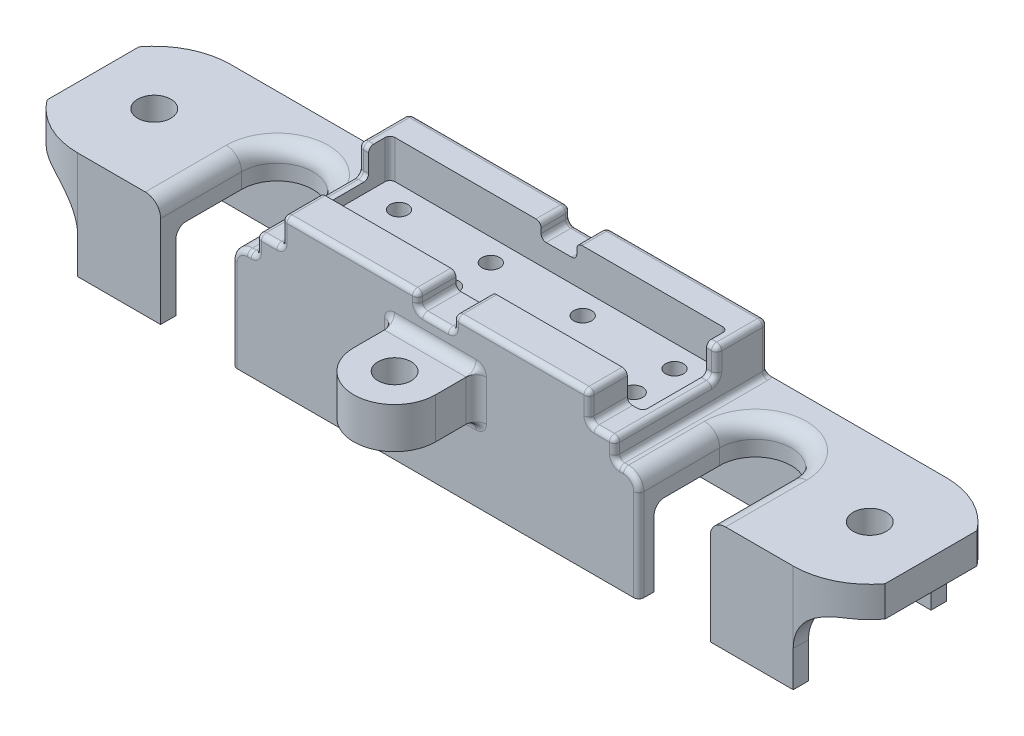
SolidWorks part; units mm, degrees
material "Delrin 2700 NC010, Low Viscosity Acetal Copolymer (SS)"
ref_plane "Front Plane" through (0, 0, 0) normal (0, 0, 1) x (1, 0, 0)
ref_plane "Top Plane" through (0, 0, 0) normal (0, 1, 0) x (1, 0, 0)
ref_plane "Right Plane" through (0, 0, 0) normal (1, 0, 0) x (0, 0, -1)
sketch "Sketch1" plane through (0, 0, 0) normal (0, 1, 0) x (1, 0, 0)
  line L1 (-35.1, -15) -> (0, -15)
  line L2 (-35.1, -15) -> (-35.1, 15)
  line L3 (-35.1, 15) -> (0, 15)
  line L4 (0, -15) -> (0, 15)
  line L5 (-35.1, -15) -> (0, 15) construction
  line L6 (-35.1, 15) -> (0, -15) construction
  point P0 (-17.55, 0)
  point P8 (0, 0)
  dimension "D1" = 35.1
  dimension "D2" = 30
extrude "Boss-Extrude1" add sketch "Sketch1" along normal blind 15.5
shell "Shell1" [suppressed] thickness 1
sketch "Sketch7" plane through (0, 15.5, 0) normal (0, 1, 0) x (1, 0, 0)
  line L0 (0, -15) -> (0, 15) construction
  line L1 (0, -7.5) -> (-33.1, -7.5)
  line L2 (0, -7.5) -> (0, 9.2)
  line L3 (0, 9.2) -> (-33.1, 9.2)
  line L4 (-33.1, -7.5) -> (-33.1, 9.2)
  line L5 (-35.1, -15) -> (0, -15) construction
  line L6 (0, 15) -> (-35.1, 15) construction
  line L7 (-35.1, 15) -> (-35.1, -15) construction
  dimension "D1" = 7.5
  dimension "D2" = 5.8
  dimension "D3" = 2
extrude "Cut-Extrude5" cut sketch "Sketch7" against normal offset from surface (7.5 mm away) 8 up to face at (-17.55, 0, 0)
sketch "Sketch2" plane through (0, 0, 0) normal (0, 1, 0) x (-1, 0, 0)
  line L0 (27, 3.15) -> (9, 3.15) construction
  line L2 (27, 3.15) -> (27, -4.85) construction
  line L3 (27, -4.85) -> (9, -4.85) construction
  line L4 (9, -4.85) -> (9, 3.15) construction
  line L5 (27, -0.85) -> (18.8977, -0.85) construction
  line L6 (17.55, -15) -> (17.55, 15) construction
  line L7 (0, 7.5) -> (0, -9.2) construction
  line L8 (27, -0.85) -> (0, -0.85) construction
  line L9 (0, -15) -> (35.1, -15) construction
  line L10 (35.1, 15) -> (0, 15) construction
  circle A0 centre (27, 3.15) radius 1.75
  circle A1 centre (9, 3.15) radius 1.75
  circle A2 centre (27, -4.85) radius 1.75
  circle A3 centre (9, -4.85) radius 1.75
  circle A5 centre (27, 3.15) radius 2.5 construction
  circle A6 centre (27, -4.85) radius 2.5 construction
  circle A7 centre (9, -4.85) radius 2.5 construction
  circle A8 centre (9, 3.15) radius 2.5 construction
  dimension "D1" = 3.5
  dimension "D4" = 9
  dimension "D5" = 5
  dimension "D2" = 18
  dimension "D3" = 8
extrude "Cut-Extrude1" cut sketch "Sketch2" along normal through all
sketch "Sketch3" [suppressed] plane through (0, 5, 0) normal (0, 1, 0) x (1, 0, 0)
  line L1 (-2.9573, -5.1559) -> (2.9865, -5.139)
  line L2 (2.9865, -5.139) -> (5.9438, 0.0169)
  line L3 (5.9438, 0.0169) -> (2.9573, 5.1559)
  line L4 (2.9573, 5.1559) -> (-2.9865, 5.139)
  line L5 (-2.9865, 5.139) -> (-5.9438, -0.0169)
  line L6 (-5.9438, -0.0169) -> (-2.9573, -5.1559)
  circle A0 centre (0, 0) radius 2.6 construction
  circle A1 centre (0, 0) radius 5.1475 construction
  dimension "D1" = 5.2
extrude "Cut-Extrude2" [suppressed] cut sketch "Sketch3" against normal blind 0.5
sketch "Sketch4" plane through (-35.1, 0, 0) normal (-1, 0, 0) x (0, 0, 1)
  line L0 (-15, 15.5) -> (15, 15.5) construction
  line L1 (-5, 15.5) -> (15, 15.5)
  line L3 (-5, 10) -> (15, 10)
  line L4 (15, 15.5) -> (15, 10)
  line L5 (0, 10) -> (0, 0) construction
  line L11 (-15, 0) -> (15, 0) construction
  line L12 (-5, 10) -> (-5, 15.5)
  dimension "D1" = 5
  dimension "D2" = 5.5
extrude "Cut-Extrude3" cut sketch "Sketch4" against normal offset from surface (5 mm away) 3 up to face at (-33.1, 11.75, -0.85) offset beyond the face yes
sketch "Sketch8" plane through (0, 0, 0) normal (0, -1, 0) x (-1, 0, 0)
  line L0 (35.1, -15) -> (70.1, -15)
  line L1 (35.1, 15) -> (70.1, 15)
  line L2 (35.1, 15) -> (35.1, -15)
  line L3 (82.1, 9) -> (82.1, -9)
  arc A0 (70.1, 15) -> (82.1, 9) centre (70.1, 0) cw
  circle A1 centre (70.1, 0) radius 3.25
  arc A2 (82.1, -9) -> (70.1, -15) centre (70.1, 0) cw
  dimension "D2" = 6.5
  dimension "D1" = 35
  dimension "D3" = 12
extrude "bolt extrude" add sketch "Sketch8" against normal blind 6
mirror "Mirror1" about plane through (0, 0, 0) normal (1, 0, 0) of bodies 112 105
fillet "Fillet3" radius 1 8 edges at (30.1, 10, 11.25) (-30.1, 10, 11.25) (30.1, 15.5, 11.25) (-30.1, 15.5, 11.25) (34.1, 15.5, -5) (34.1, 10, -5) (-34.1, 15.5, -5) (-34.1, 10, -5)
fillet "Fillet5" [suppressed] radius 0.5
sketch "Sketch9" plane through (0, 15.5, 0) normal (0, 1, 0) x (1, 0, 0)
  line L0 (35.1, 15) -> (-35.1, 15) construction
  line L1 (-3.5, 15) -> (3.5, 15)
  line L2 (-3.5, 15) -> (-3.5, -15)
  line L3 (-3.5, -15) -> (3.5, -15)
  line L4 (3.5, 15) -> (3.5, -15)
  line L5 (-29.1, -15) -> (29.1, -15) construction
  dimension "D1" = 3.5
  dimension "D2" = 3.5
extrude "Cut-Extrude6" cut sketch "Sketch9" against normal blind 3
fillet "Fillet6" radius 1 14 edges at (35.1, 10.75, -15) (-35.1, 10.75, -15) (-33.1, 9, 7.5) (-33.1, 11.75, -9.2) (33.1, 11.75, -9.2) (33.1, 9, 7.5) (-3.5, 12.5, -12.1) (3.5, 12.5, -12.1) (3.5, 12.5, 11.25) (-3.5, 12.5, 11.25) (3.5, 15.5, 11.25) (-3.5, 15.5, 11.25) (-3.5, 15.5, -12.1) (3.5, 15.5, -12.1)
fillet "Fillet7" [suppressed] radius 1
fillet "Fillet9" radius 1 25 edges at (-35.1, 10, 5.5) (35.1, 6, 0.5) (34.8071, 6, -14.7071) (35.1, 10, 5.5) (35.1, 10.2929, -4.7071) (35.1, 12.75, -5) (35.1, 15.2071, -5.2929) (35.1, 15.5, -10) (34.8071, 15.5, -14.7071) (19.3, 15.5, -15) (3.7929, 15.2071, -15) (3.5, 14, -15) (3.2071, 12.7929, -15) (0, 12.5, -15) (-3.2071, 12.7929, -15) (-3.5, 14, -15) (-3.7929, 15.2071, -15) (-19.3, 15.5, -15) (-34.8071, 15.5, -14.7071) (-35.1, 15.5, -10) (-35.1, 15.2071, -5.2929) (-35.1, 12.75, -5) (-35.1, 10.2929, -4.7071) (-34.8071, 6, -14.7071) (-35.1, 6, 0.5)
sketch "Sketch11" plane through (0, 0, 0) normal (0, -1, 0) x (1, 0, 0)
  line L0 (70.1, -15) -> (-70.1, -15) construction
  line L1 (-70.1, 15) -> (70.1, 15) construction
  line L2 (70.1, -15) -> (-70.1, -15)
  line L3 (-70.1, 15) -> (70.1, 15)
  line L4 (-70.1, 12) -> (70.1, 12)
  line L5 (70.1, -12) -> (-70.1, -12)
  line L6 (-70.1, 12) -> (-70.1, 15)
  line L7 (-70.1, -15) -> (-70.1, -12)
  line L8 (70.1, 12) -> (70.1, 15)
  line L9 (70.1, -12) -> (70.1, -15)
  point P9 (70.1, 13.5)
  dimension "D1" = 3
extrude "Boss-Extrude3" add sketch "Sketch11" along normal blind 15
sketch "Sketch12" plane through (0, 0, 0) normal (0, -1, 0) x (1, 0, 0)
  line L0 (-8, 15) -> (-8, 23)
  line L2 (8, 23) -> (8, 15)
  line L3 (8, 15) -> (-8, 15)
  line L4 (70.1, 15) -> (-70.1, 15) construction
  arc A0 (-8, 23) -> (8, 23) centre (0, 23) cw
  circle A1 centre (0, 23) radius 3.25
  point P6 (0, 15)
  dimension "D1" = 6.5
  dimension "D2" = 8
  dimension "D3" = 8
extrude "Boss-Extrude4" add sketch "Sketch12" against normal blind 8
sketch "Sketch10" plane through (0, 0, 0) normal (0, -1, 0) x (-1, 0, 0)
  line L0 (-39.85, 0.85) -> (-39.85, -15)
  line L1 (70.1, -15) -> (-70.1, -15) construction
  line L2 (-53.85, 0.85) -> (-53.85, -15)
  line L3 (39.85, 0.85) -> (39.85, -15)
  line L4 (53.85, 0.85) -> (53.85, -15)
  line L5 (-53.85, -15) -> (-39.85, -15)
  line L6 (39.85, -15) -> (53.85, -15)
  arc A0 (53.85, 0.85) -> (39.85, 0.85) centre (46.85, 0.85) ccw
  arc A1 (-39.85, 0.85) -> (-53.85, 0.85) centre (-46.85, 0.85) ccw
  dimension "D1" = 14
extrude "Cut-Extrude7" cut sketch "Sketch10" against normal through all and the other way through all
fillet "Fillet10" radius 3 6 edges at (-53.85, 6, 7.075) (-46.85, 6, -7.85) (39.85, 6, 7.075) (46.85, 6, -7.85) (-39.85, 6, 7.075) (53.85, 6, 7.075)
fillet "Fillet11" radius 8 4 edges at (70.1, 0, 13.5) (-70.1, 0, 13.5) (-70.1, 0, -13.5) (70.1, 0, -13.5)
fillet "Fillet12" radius 2 4 edges at (-65.975, 0, 12) (65.975, 0, 12) (0, 0, 12) (0, 0, -12)
fillet "Fillet13" radius 2 4 edges at (0, 8, 15) (8, 4, 15) (-8, 4, 15) (0, 0, 15)
fillet "Fillet14" radius 1 29 edges at (-39.85, -6, 15) (-38.9713, 5.1213, 15) (-36.475, 6, 15) (-35.3929, 6.2929, 15) (-35.1, 8, 15) (-34.8071, 9.7071, 15) (-32.6, 10, 15) (-30.3929, 10.2929, 15) (-30.1, 12.75, 15) (-29.8071, 15.2071, 15) (39.85, -6, 15) (38.9713, 5.1213, 15) (36.475, 6, 15) (35.3929, 6.2929, 15) (35.1, 8, 15) (34.8071, 9.7071, 15) (32.6, 10, 15) (30.3929, 10.2929, 15) (30.1, 12.75, 15) (29.8071, 15.2071, 15) (16.8, 15.5, 15) (3.7929, 15.2071, 15) (3.5, 14, 15) (3.2071, 12.7929, 15) (0, 12.5, 15) (-3.2071, 12.7929, 15) (-3.5, 14, 15) (-3.7929, 15.2071, 15) (-16.8, 15.5, 15)
